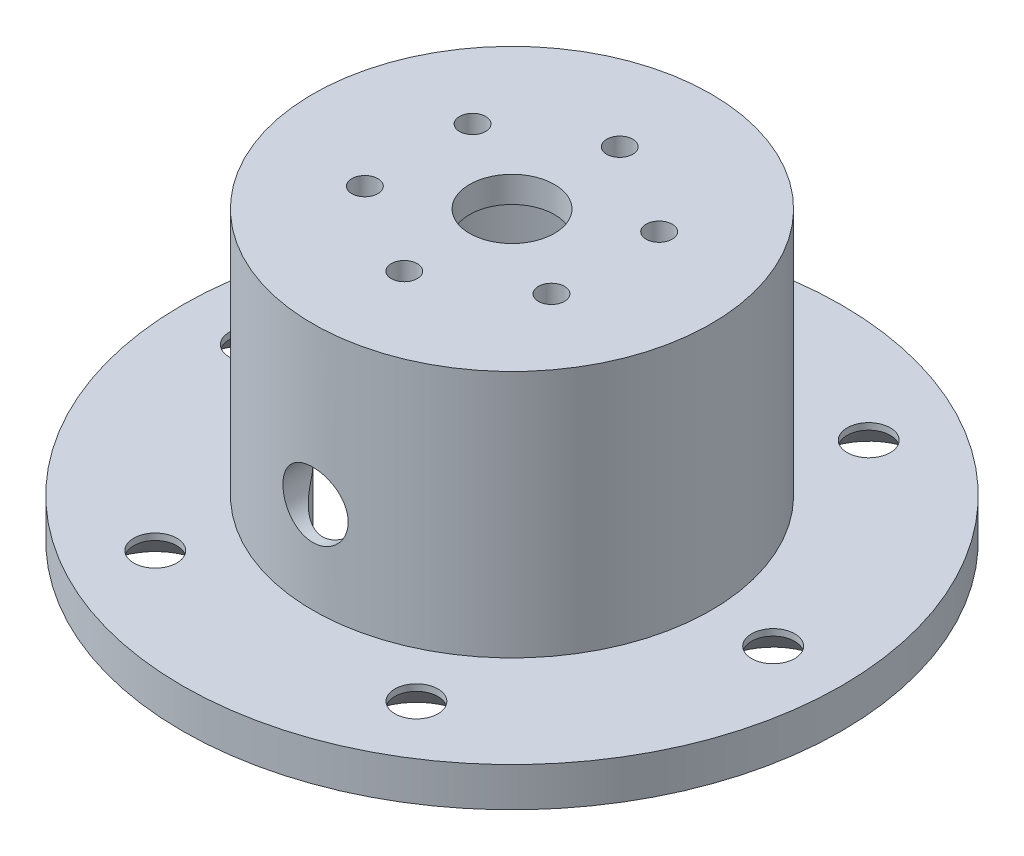
SolidWorks part; units mm, degrees
ref_plane "Front Plane" through (0, 0, 0) normal (0, 0, 1) x (1, 0, 0)
ref_plane "Top Plane" through (0, 0, 0) normal (0, 1, 0) x (1, 0, 0)
ref_plane "Right Plane" through (0, 0, 0) normal (1, 0, 0) x (0, 0, -1)
sketch "Sketch1" plane through (0, 0, 0) normal (0, 0, 1) x (1, 0, 0)
  line L0 (0, -8.7813) -> (0, 7.1563) construction
  line L1 (3.25, 10) -> (3.25, 12)
  line L2 (3.25, 12) -> (15.25, 12)
  line L3 (15.25, 12) -> (15.25, -7)
  line L4 (15.25, -7) -> (25.25, -7)
  line L5 (25.25, -7) -> (25.25, -10)
  line L6 (25.25, -10) -> (13, -10)
  line L7 (13, -10) -> (13, 10)
  line L8 (13, 10) -> (3.25, 10)
  point P5 (13, 0)
  dimension "D1" = 2
  dimension "D2" = 30.5
  dimension "D3" = 3
  dimension "D4" = 6.5
  dimension "D5" = 26
  dimension "D6" = 20
  dimension "D7" = 10
revolve "Revolve1" add sketch "Sketch1" angle 360 about L0
sketch "Sketch2" plane through (0, 12, 0) normal (0, 1, 0) x (1, 0, 0)
  line L0 (-6.118, 0) -> (7.121, 0) construction
  circle A0 centre (0, 8.25) radius 1
  circle A1 centre (20, 0) radius 1.65
  dimension "D2" = 2
  dimension "D3" = 3.3
  dimension "D1" = 16.5
  dimension "D4" = 20
extrude "Cut-Extrude1" cut sketch "Sketch2" against normal through all
chamfer "Chamfer2" distance 2.5 angle 45 1 edges at (20, -10, 1.65)
pattern_circular "CirPattern1" count 6 over 360 about axis through (0, -8.7813, 0) along (0, -1, 0) of "Cut-Extrude1", "Chamfer2" reverse direction yes
sketch "Sketch3" plane through (0, 0, 0) normal (0, 0, 1) x (1, 0, 0)
  line L0 (-13, 10) -> (13, 10) construction
  circle A0 centre (0, 0) radius 2.5
  dimension "D2" = 5
  dimension "D1" = 10
extrude "Cut-Extrude2" cut sketch "Sketch3" along normal through all
sketch "Sketch4" plane through (0, -10, 0) normal (0, -1, 0) x (1, 0, 0)
  arc A0 (2.5, 12.7574) -> (-2.5, 12.7574) centre (0, 0) ccw construction
  arc A1 (2.5, 12.7574) -> (-2.5, 12.7574) centre (0, 0) ccw
  arc A2 (2.5, 12.7574) -> (-2.5, 12.7574) centre (0, 11.8354) ccw
  point P4 (0, 14.5)
  point P5 (0, 13)
  dimension "D1" = 1.5
extrude "Cut-Extrude3" cut sketch "Sketch4" against normal blind 10
